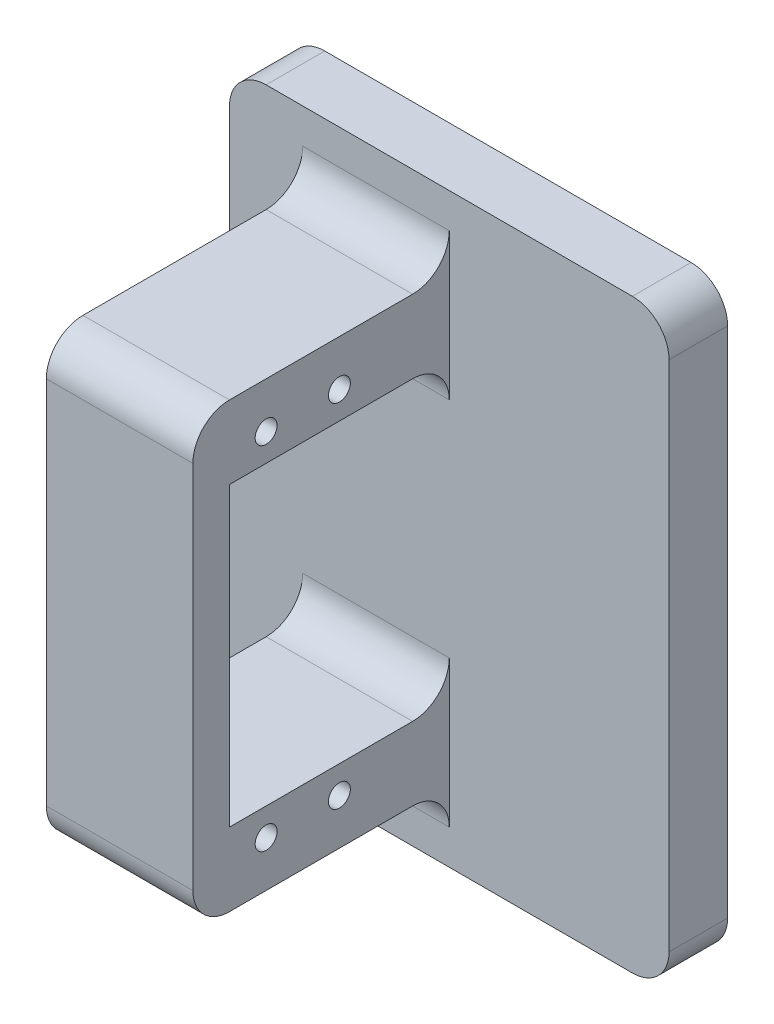
SolidWorks part; units mm, degrees
ref_plane "Front Plane" through (0, 0, 0) normal (0, 0, 1) x (1, 0, 0)
ref_plane "Top Plane" through (0, 0, 0) normal (0, 1, 0) x (1, 0, 0)
ref_plane "Right Plane" through (0, 0, 0) normal (1, 0, 0) x (0, 0, -1)
sketch "Sketch3" plane through (0, 0, 30) normal (0, 0, -1) x (-1, 0, 0)
  line L0 (95, 33.2573) -> (65, 33.2573) construction
  line L15 (80, 53.2573) -> (80, 33.2573) construction
  line L20 (55, 53.2573) -> (105, 53.2573)
  line L29 (55, -26.7427) -> (105, -26.7427)
  line L31 (110, -21.7427) -> (110, 48.2573)
  line L33 (50, -21.7427) -> (50, 48.2573)
  arc A17 (50, 48.2573) -> (55, 53.2573) centre (55, 48.2573) cw
  arc A18 (110, 48.2573) -> (105, 53.2573) centre (105, 48.2573) ccw
  arc A21 (50, -21.7427) -> (55, -26.7427) centre (55, -21.7427) ccw
  arc A22 (110, -21.7427) -> (105, -26.7427) centre (105, -21.7427) cw
  dimension "D1" = 5
extrude "Boss-Extrude1" add sketch "Sketch3" along normal blind 8
ref_plane "Plane1" through (-80, 0, 0) normal (-1, 0, 0) x (0, 0, 1)
sketch "Sketch8" plane through (0, 0, 22) normal (0, 0, -1) x (-1, 0, 0)
  line L0 (50, 13.2573) -> (110, 13.2573) construction
  line L1 (50, 48.2573) -> (50, -21.7427) construction
  line L2 (110, -21.7427) -> (110, 48.2573) construction
  line L3 (80, 13.2573) -> (80, -26.7427) construction
  line L4 (55, -26.7427) -> (105, -26.7427) construction
  line L5 (78.25, 15.3786) -> (78.25, 11.136)
  line L6 (81.75, 15.3786) -> (81.75, 11.136)
  arc A0 (78.25, 11.136) -> (81.75, 11.136) centre (80, 13.2573) ccw
  arc A1 (81.75, 15.3786) -> (78.25, 15.3786) centre (80, 13.2573) ccw
extrude "Cut-Extrude3" cut sketch "Sketch8" against normal blind 3
sketch "Sketch10" plane through (0, 0, 22) normal (0, 0, -1) x (-1, 0, 0)
  line L0 (50, 13.2573) -> (110, 13.2573) construction
  line L1 (50, 48.2573) -> (50, -21.7427) construction
  line L2 (110, -21.7427) -> (110, 48.2573) construction
  line L3 (80, 13.2573) -> (80, -26.7427) construction
  line L4 (55, -26.7427) -> (105, -26.7427) construction
  line L7 (81.75, 11.136) -> (81.75, 15.3786)
  line L8 (78.25, 15.3786) -> (78.25, 11.136)
  line L9 (81.75, 11.136) -> (81.75, 15.3786)
  line L10 (78.25, 15.3786) -> (78.25, 11.136)
  circle A3 centre (80, 13.2573) radius 9.75
  arc A5 (78.25, 11.136) -> (81.75, 11.136) centre (80, 13.2573) ccw
  arc A6 (81.75, 15.3786) -> (78.25, 15.3786) centre (80, 13.2573) ccw
  arc A7 (78.25, 11.136) -> (81.75, 11.136) centre (80, 13.2573) ccw
  arc A8 (81.75, 15.3786) -> (78.25, 15.3786) centre (80, 13.2573) ccw
  dimension "D1" = 0
extrude "Boss-Extrude4" add sketch "Sketch10" along normal blind 9
sketch "Sketch12" plane through (-80, 0, 0) normal (-1, 0, 0) x (0, 0, 1)
  line L0 (60, -6.9927) -> (40, -6.9927) construction
  line L1 (60, 33.5073) -> (60, -6.9927) construction
  line L2 (40, 33.5073) -> (60, 33.5073) construction
  line L3 (60, -6.9927) -> (30, -6.9927)
  line L4 (60, 33.5073) -> (60, -6.9927)
  line L5 (30, 33.5073) -> (60, 33.5073)
  line L6 (30, -21.7427) -> (30, 48.2573) construction
  line L7 (30, 43.5073) -> (65, 43.5073)
  line L8 (65, 43.5073) -> (65, -16.9927)
  line L9 (65, -16.9927) -> (30, -16.9927)
  line L10 (30, -16.9927) -> (30, -6.9927)
  line L11 (30, 33.5073) -> (30, 43.5073)
  dimension "D1" = 10
  dimension "D2" = 10
  dimension "D3" = 5
extrude "Boss-Extrude5" add sketch "Sketch12" along normal blind 20
fillet "Fillet1" radius 5 6 edges at (-90, -16.9927, 30) (-90, -6.9927, 30) (-90, 33.5073, 30) (-90, 43.5073, 30) (-90, 43.5073, 65) (-90, -16.9927, 65)
sketch "Sketch13" plane through (-80, 0, 0) normal (1, 0, 0) x (0, 0, -1)
  circle A0 centre (-55, -10.7427) radius 1.5
  circle A1 centre (-45, -10.7427) radius 1.5
  circle A2 centre (-55, 37.2573) radius 1.5
  circle A3 centre (-45, 37.2573) radius 1.5
extrude "Cut-Extrude4" cut sketch "Sketch13" against normal blind 10
